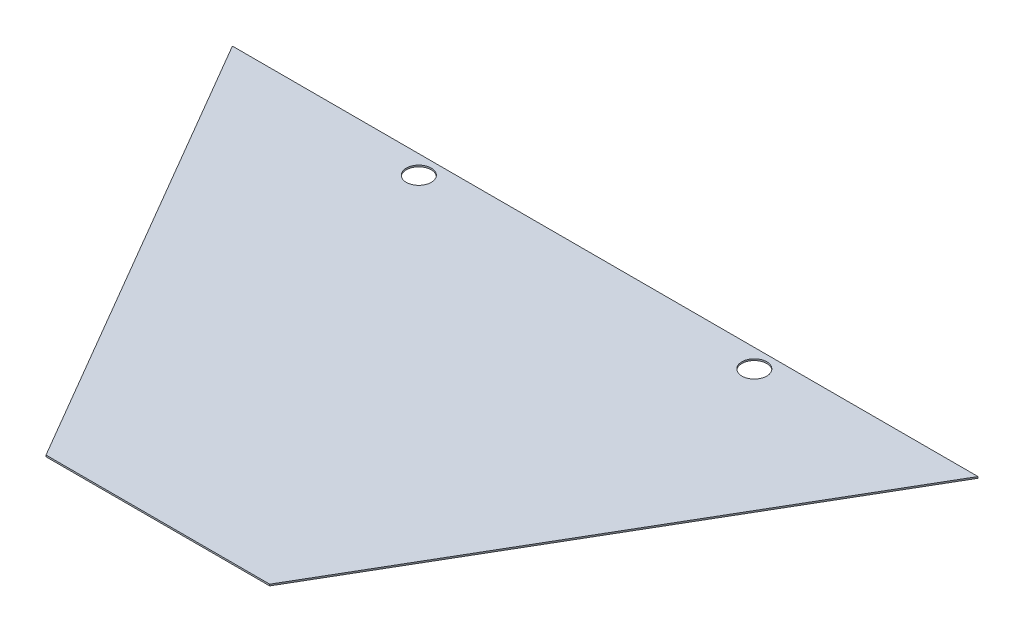
SolidWorks part; units mm, degrees
ref_plane "Front Plane" through (0, 0, 0) normal (0, 0, 1) x (1, 0, 0)
ref_plane "Top Plane" through (0, 0, 0) normal (0, 1, 0) x (1, 0, 0)
ref_plane "Right Plane" through (0, 0, 0) normal (1, 0, 0) x (0, 0, -1)
sketch "Sketch1" plane through (0, 0, 0) normal (0, 1, 0) x (1, 0, 0)
  line L0 (0, 0) -> (457.2, 0)
  line L1 (457.2, 0) -> (990.6, 914.4)
  line L3 (990.6, 914.4) -> (-533.4, 914.4)
  line L5 (-533.4, 914.4) -> (0, 0)
  line L6 (228.6, 914.4) -> (228.6, 0) construction
  dimension "D1" = 457.2
  dimension "D2" = 914.4
  dimension "D4" = 1524
extrude "Boss-Extrude1" add sketch "Sketch1" along normal blind 3.175
sketch "Sketch2" plane through (0, 3.175, 0) normal (0, 1, 0) x (-1, 0, 0)
  line L0 (-228.6, -914.4) -> (-228.6, 0) construction
  line L1 (-990.6, -914.4) -> (533.4, -914.4) construction
  line L2 (0, 0) -> (-457.2, 0) construction
  circle A0 centre (114.3, -876.3) radius 25.4
  circle A1 centre (-571.5, -876.3) radius 25.4
  dimension "D1" = 342.9
  dimension "D2" = 50.8
  dimension "D3" = 38.1
extrude "Cut-Extrude1" cut sketch "Sketch2" against normal up to next
